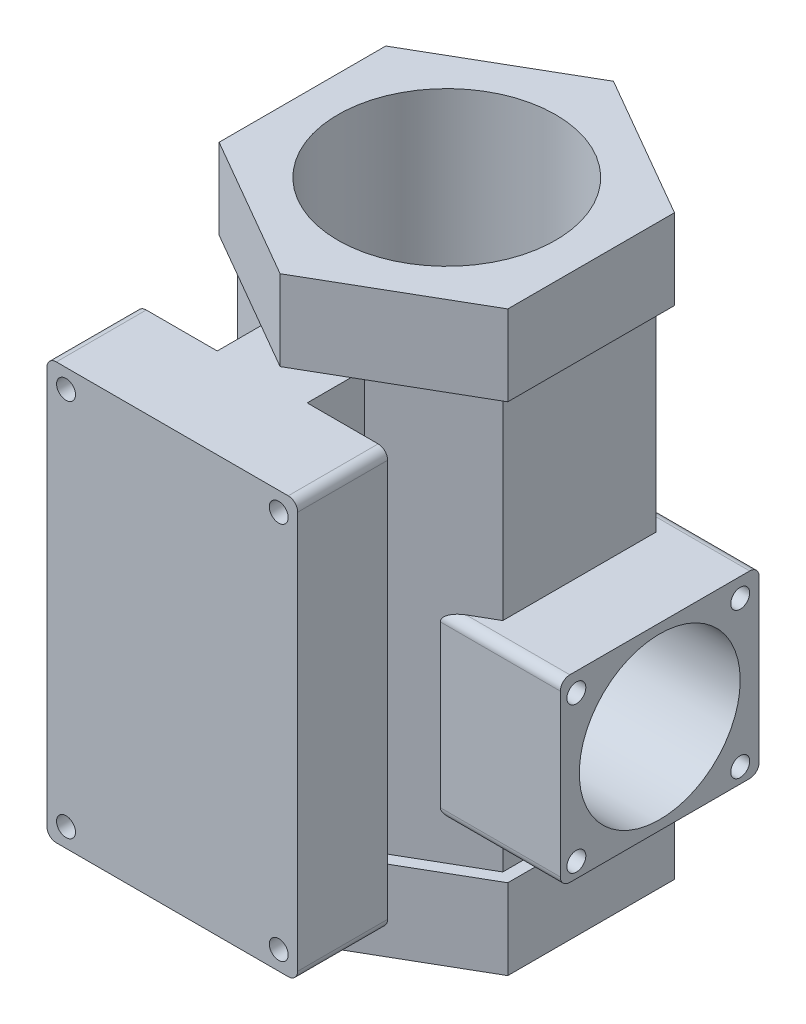
SolidWorks part; units mm, degrees
ref_plane "Спереди" through (0, 0, 0) normal (0, 0, 1) x (1, 0, 0)
ref_plane "Сверху" through (0, 0, 0) normal (0, 1, 0) x (1, 0, 0)
ref_plane "Справа" through (0, 0, 0) normal (1, 0, 0) x (0, 0, -1)
sketch "Эскиз центра" plane through (0, 0, 0) normal (0, 1, 0) x (1, 0, 0)
  line L0 (0, 0) -> (0, -290) construction
  line L1 (0, 161.6581) -> (-140, 80.829)
  line L2 (-140, 80.829) -> (-140, -80.829)
  line L3 (-140, -80.829) -> (-47.5, -134.2339)
  line L4 (47.5, -134.2339) -> (140, -80.829)
  line L5 (140, -80.829) -> (140, 80.829)
  line L6 (140, 80.829) -> (0, 161.6581)
  line L7 (132.5, -290) -> (-132.5, -290)
  line L8 (-132.5, -290) -> (-132.5, -195)
  line L9 (-132.5, -195) -> (-47.5, -195)
  line L10 (-47.5, -195) -> (-47.5, -134.2339)
  line L11 (47.5, -195) -> (47.5, -134.2339)
  line L12 (132.5, -195) -> (47.5, -195)
  line L13 (132.5, -290) -> (132.5, -195)
  circle A0 centre (0, 0) radius 140 construction
sketch "Эскиз2" plane through (0, 0, 0) normal (0, 1, 0) x (1, 0, 0)
  line L1 (0, 176.0918) -> (-152.5, 88.0459)
  line L2 (-152.5, 88.0459) -> (-152.5, -88.0459)
  line L3 (-152.5, -88.0459) -> (0, -176.0918)
  line L4 (0, -176.0918) -> (152.5, -88.0459)
  line L5 (152.5, -88.0459) -> (152.5, 88.0459)
  line L6 (152.5, 88.0459) -> (0, 176.0918)
  circle A0 centre (0, 0) radius 152.5 construction
extrude "Боковой многогранник 1" add sketch "Эскиз2" along normal blind 85
extrude "Центральная часть" add sketch "Эскиз центра" against normal blind 440
sketch "Эскиз4" plane through (0, -440, 0) normal (0, -1, 0) x (1, 0, 0)
  line L1 (0, -176.0918) -> (152.5, -88.0459)
  line L2 (152.5, -88.0459) -> (152.5, 88.0459)
  line L3 (152.5, 88.0459) -> (0, 176.0918)
  line L4 (0, 176.0918) -> (-152.5, 88.0459)
  line L5 (-152.5, 88.0459) -> (-152.5, -88.0459)
  line L6 (-152.5, -88.0459) -> (0, -176.0918)
  circle A0 centre (0, 0) radius 152.5 construction
extrude "Боковой многогранник 2" add sketch "Эскиз4" along normal blind 85
sketch "Эскиз5" plane through (0, 85, 0) normal (0, 1, 0) x (1, 0, 0)
  circle A0 centre (0, 0) radius 115
sketch "Эскиз10" plane through (140, 0, 0) normal (1, 0, 0) x (0, 0, -1)
  line L2 (-105, -210) -> (105, -210)
  line L3 (-105, -210) -> (-105, -400)
  line L4 (-105, -400) -> (105, -400)
  line L5 (105, -210) -> (105, -400)
  line L6 (-105, -210) -> (105, -400) construction
  line L7 (-105, -400) -> (105, -210) construction
  point P0 (0, -305)
extrude "Боковой фланц" add sketch "Эскиз10" along normal blind 85 and the other way blind 140
extrude "Центральный вырез" cut sketch "Эскиз5" against normal through all contours A0
sketch "Эскиз12" plane through (225, 0, 0) normal (1, 0, 0) x (0, 0, -1)
  circle A0 centre (0, -305) radius 85
extrude "Боковой вырез" cut sketch "Эскиз12" against normal up to next
sketch "Эскиз13" plane through (0, 0, 290) normal (0, 0, 1) x (1, 0, 0)
  circle A0 centre (-112.2324, -420.0794) radius 10
  circle A1 centre (112.5, -420.0794) radius 10
  circle A2 centre (-112.2324, -20) radius 10
  circle A3 centre (112.5, -20) radius 10
extrude "Отверстия в основании" cut sketch "Эскиз13" against normal up to next
sketch "Эскиз14" plane through (225, 0, 0) normal (1, 0, 0) x (0, 0, -1)
  circle A0 centre (85, -230) radius 10
  circle A1 centre (85, -384.038) radius 10
  circle A2 centre (-88.1172, -230) radius 10
  circle A3 centre (-88.1172, -384.038) radius 10
extrude "Вырез-Вытянуть6" cut sketch "Эскиз14" against normal blind 30
fillet "Скругление2" radius 10 4 edges at (-132.5, -440, 242.5) (132.5, -440, 242.5) (-132.5, 0, 242.5) (132.5, 0, 242.5)
fillet "Скругление3" radius 10 4 edges at (161.5673, -210, -105) (161.5673, -400, -105) (161.5673, -400, 105) (161.5673, -210, 105)
